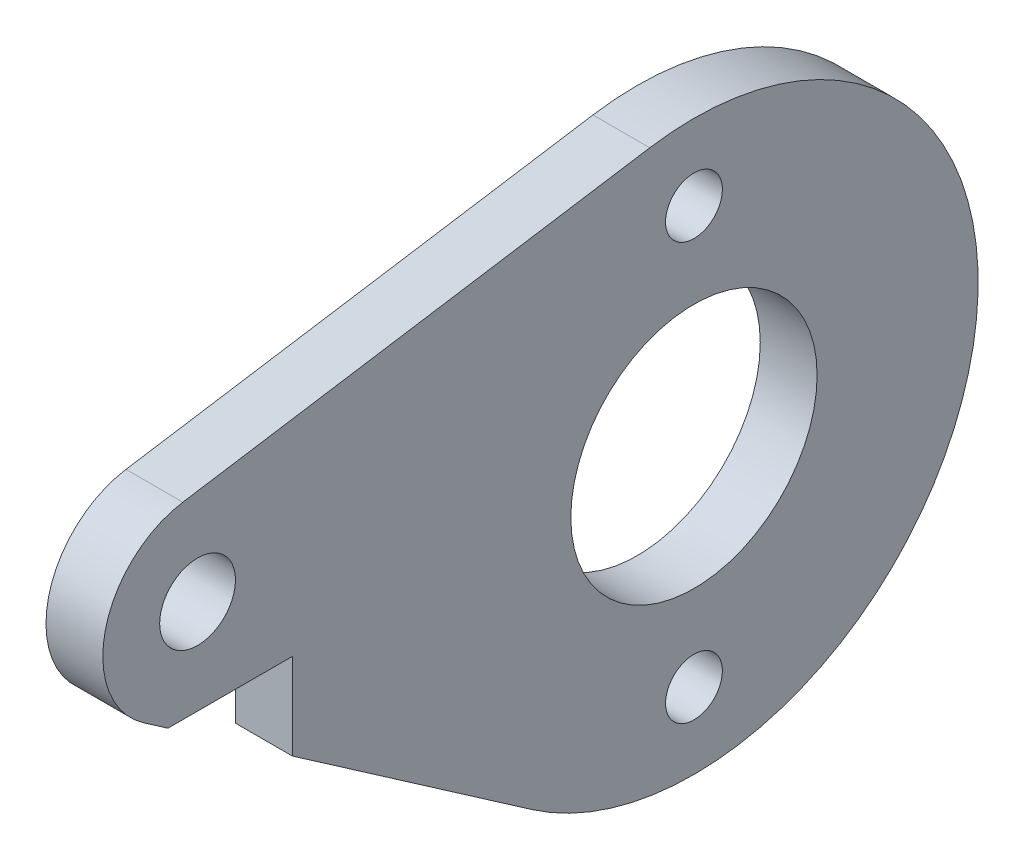
SolidWorks part; units mm, degrees
ref_plane "Plan de face" through (0, 0, 0) normal (0, 0, 1) x (1, 0, 0)
ref_plane "Plan de dessus" through (0, 0, 0) normal (0, 1, 0) x (1, 0, 0)
ref_plane "Plan de droite" through (0, 0, 0) normal (1, 0, 0) x (0, 0, -1)
sketch "Esquisse1" plane through (0, 0, 0) normal (-1, 0, 0) x (0, 0, 1)
  line L0 (29.0493, 1.8913) -> (8.548, -12.3261)
  line L1 (2.3318, 14.8176) -> (26.9773, 10.9392)
  arc A0 (8.548, -12.3261) -> (2.3318, 14.8176) centre (0, 0) cw
  arc A1 (26.9773, 10.9392) -> (29.0493, 1.8913) centre (26.2, 6) cw
  circle A2 centre (0, 0) radius 6.5 construction
  circle A3 centre (0, 0) radius 6.5
  circle A5 centre (0, 11) radius 1.5
  circle A6 centre (0, -11) radius 1.5
  circle A7 centre (0, 0) radius 15 construction
  circle A8 centre (26.2, 6) radius 2
  dimension "D1" = 3
  dimension "D2" = 4
  dimension "D3" = 5
extrude "Boss.-Extru.1" add sketch "Esquisse1" against normal blind 3
sketch "Esquisse2" plane through (3, 0, 0) normal (1, 0, 0) x (0, 0, -1)
  line L0 (-27.7641, 1) -> (-21.2, 1)
  line L1 (-8.548, -12.3261) -> (-29.0493, 1.8913) construction
  line L2 (-21.2, 1) -> (-21.2, -3.5521)
  line L3 (-21.2, -3.5521) -> (-27.7641, 1)
  line L4 (-21.2, 1) -> (-31.2, 1) construction
  line L5 (-21.2, 1) -> (-21.2, -9) construction
extrude "Enlèv. mat.-Extru.1" cut sketch "Esquisse2" against normal through all
